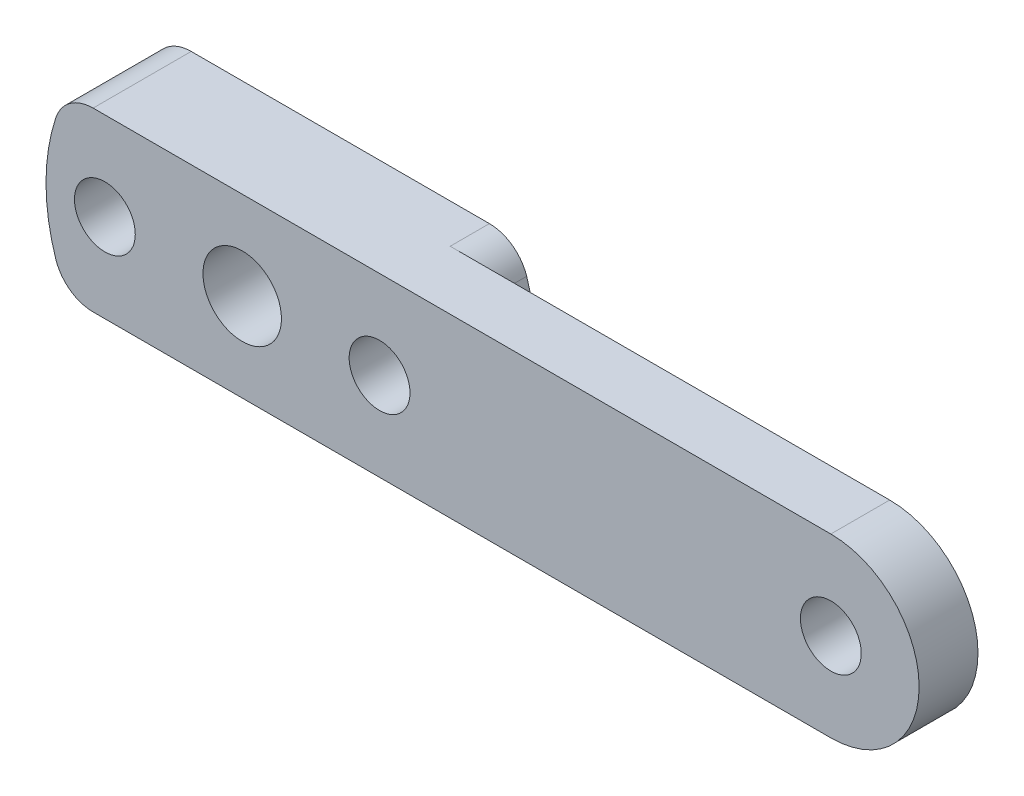
SolidWorks part; units mm, degrees
ref_plane "Front Plane" through (0, 0, 0) normal (0, 0, 1) x (1, 0, 0)
ref_plane "Top Plane" through (0, 0, 0) normal (0, 1, 0) x (1, 0, 0)
ref_plane "Right Plane" through (0, 0, 0) normal (1, 0, 0) x (0, 0, -1)
sketch "Sketch1" plane through (0, 0, 0) normal (0, 0, 1) x (1, 0, 0)
  line L0 (-8.9303, 4.5) -> (30, 4.5)
  line L1 (30, -4.5) -> (-8.9303, -4.5)
  line L2 (-7, 0) -> (7, 0) construction
  arc A0 (-8.9303, -4.5) -> (-8.9303, 4.5) centre (0, 0) cw
  arc A1 (30, 4.5) -> (30, -4.5) centre (30, 0) cw
  circle A2 centre (-7, 0) radius 1.55
  circle A3 centre (7, 0) radius 1.55
  circle A4 centre (30, 0) radius 1.55
  circle A5 centre (0, 0) radius 2
  point P6 (-10, 0)
  point P12 (0, 0)
  dimension "D1" = 10
  dimension "D2" = 9
  dimension "D4" = 3.1
  dimension "D6" = 4
  dimension "D3" = 30
  dimension "D5" = 14
extrude "Boss-Extrude1" add sketch "Sketch1" along normal mid plane 5
sketch "Sketch2" plane through (0, 0, -2.5) normal (0, 0, -1) x (-1, 0, 0)
  line L0 (8.9303, -4.5) -> (-30, -4.5) construction
  line L1 (-30, 4.5) -> (8.9303, 4.5) construction
  line L2 (-30, 4.5) -> (-8.9303, 4.5)
  line L3 (-8.9303, -4.5) -> (-30, -4.5)
  arc A0 (-30, 4.5) -> (-30, -4.5) centre (-30, 0) ccw construction
  arc A1 (-30, 4.5) -> (-30, -4.5) centre (-30, 0) ccw
  arc A2 (-8.9303, -4.5) -> (-8.9303, 4.5) centre (0, 0) cw
  dimension "D1" = 10
extrude "Cut-Extrude1" cut sketch "Sketch2" against normal offset from surface (2 mm away) 3 up to face at (11.3924, 0, 2.5)
fillet "Fillet1" radius 2 4 edges at (-8.9303, -4.5, 0) (-8.9303, 4.5, 0) (8.9303, -4.5, -1.5) (8.9303, 4.5, -1.5)
sketch "Sketch3" plane through (0, 0, -2.5) normal (0, 0, -1) x (-1, 0, 0)
  point P0 (0, 0)
